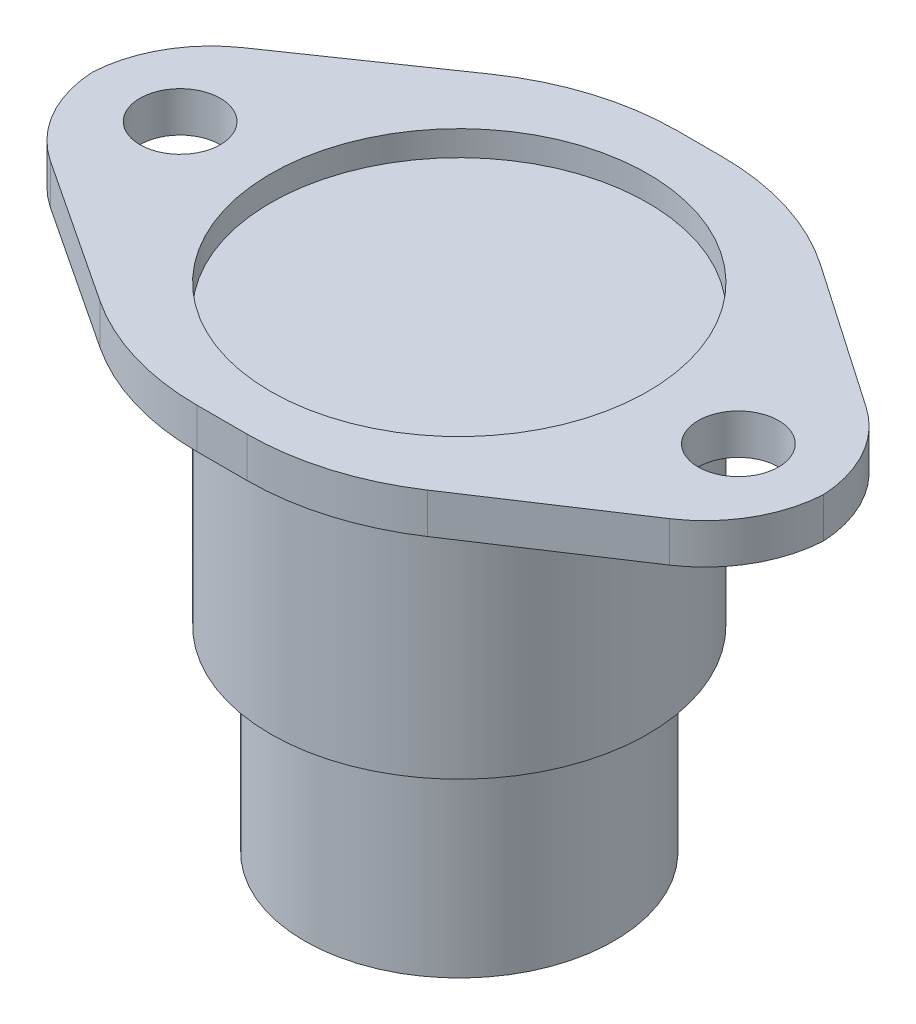
SolidWorks part; units mm, degrees
ref_plane "Front Plane" through (0, 0, 0) normal (0, 0, 1) x (1, 0, 0)
ref_plane "Top Plane" through (0, 0, 0) normal (0, 1, 0) x (1, 0, 0)
ref_plane "Right Plane" through (0, 0, 0) normal (1, 0, 0) x (0, 0, -1)
sketch "Sketch1" plane through (0, 0, 0) normal (0, 1, 0) x (1, 0, 0)
  circle A0 centre (0, 0) radius 7.5
  dimension "D1" = 15
extrude "Boss-Extrude1" add sketch "Sketch1" along normal blind 10.2
sketch "Sketch2" plane through (0, 10.2, 0) normal (0, 1, 0) x (1, 0, 0)
  line L0 (0, 0) -> (0, 12.4896) construction
  line L1 (0, 0) -> (15.6875, 0) construction
  line L2 (-14.55, 2.307) -> (-14.55, -2.4661)
  line L3 (-14.55, -2.4661) -> (-4, -9.4348)
  line L4 (-4, -9.4348) -> (4, -9.4348)
  line L5 (4, -9.4348) -> (14.55, -2.4661)
  line L6 (14.55, -2.4661) -> (14.55, 2.307)
  line L7 (14.55, 2.307) -> (4, 9.5652)
  line L8 (4, 9.5652) -> (-4, 9.5652)
  line L9 (-4, 9.5652) -> (-14.55, 2.307)
  circle A0 centre (-11.1, 0) radius 1.6
  circle A1 centre (11.1, 0) radius 1.6
  dimension "D3" = 3.2
  dimension "D1" = 29.1
  dimension "D2" = 19
  dimension "D4" = 22.2
  dimension "D5" = 8
extrude "Boss-Extrude2" add sketch "Sketch2" along normal blind 1.6
sketch "Sketch3" plane through (0, 0, 0) normal (0, -1, 0) x (1, 0, 0)
  circle A0 centre (0, 0) radius 6.15
  dimension "D1" = 12.3
extrude "Boss-Extrude3" add sketch "Sketch3" along normal blind 7.8
sketch "Sketch4" plane through (0, 11.8, 0) normal (0, 1, 0) x (1, 0, 0)
  circle A0 centre (0, 0) radius 7.5
  dimension "D1" = 15
extrude "Cut-Extrude1" cut sketch "Sketch4" against normal blind 1
fillet "Fillet1" radius 5 4 edges at (14.55, 11, -2.307) (14.55, 11, 2.4661) (-14.55, 11, -2.307) (-14.55, 11, 2.4661)
fillet "Fillet2" radius 10 4 edges at (4, 11, -9.5652) (-4, 11, -9.5652) (4, 11, 9.4348) (-4, 11, 9.4348)
